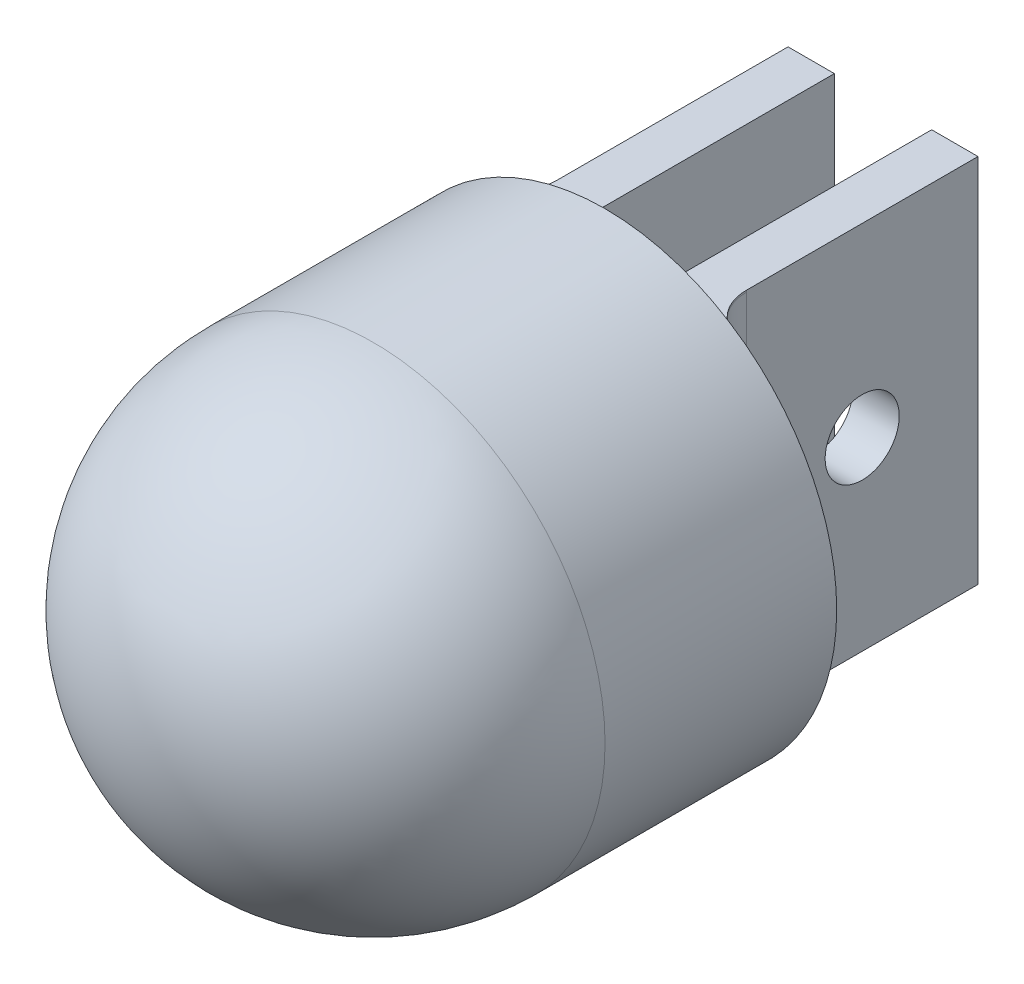
SolidWorks part; units mm, degrees
ref_plane "Front" through (0, 0, 0) normal (0, 0, 1) x (1, 0, 0)
ref_plane "Top" through (0, 0, 0) normal (0, 1, 0) x (1, 0, 0)
ref_plane "Right" through (0, 0, 0) normal (1, 0, 0) x (0, 0, -1)
sketch "草图2" plane through (0, 0, 0) normal (0, 1, 0) x (1, 0, 0)
  line L0 (0, 0) -> (0, 11.3858) construction
  line L1 (0, 10) -> (-5, 10)
  line L2 (-5, 10) -> (-5, 5)
  line L3 (0, 0) -> (0, 10)
  arc A0 (-5, 5) -> (0, 0) centre (0, 5) ccw
  point P8 (-2.5, 10)
  dimension "D2" = 10
  dimension "D1" = 10
revolve "旋转1" add sketch "草图2" angle 360 about L0
sketch "草图3" plane through (0, 0, -10) normal (0, 0, -1) x (-1, 0, 0)
  line L0 (0, 0) -> (0, 3.9434) construction
  line L1 (-2.05, 4) -> (-1.05, 4)
  line L2 (-2.05, 4) -> (-2.05, -4)
  line L3 (-2.05, -4) -> (-1.05, -4)
  line L4 (-1.05, 4) -> (-1.05, -4)
  line L5 (1.05, 4) -> (2.05, 4)
  line L6 (1.05, 4) -> (1.05, -4)
  line L7 (1.05, -4) -> (2.05, -4)
  line L8 (2.05, 4) -> (2.05, -4)
  line L9 (-1.05, 0) -> (1.05, 0) construction
  dimension "D1" = 2.1
  dimension "D2" = 1
  dimension "D3" = 1
  dimension "D4" = 8
extrude "凸台-拉伸1" add sketch "草图3" along normal blind 6
hole_wizard "M2 螺纹孔1" positions "草图4" profile "草图5" tap size "M2" standard "GB"
sketch "草图4" plane through (-2.05, 0, 0) normal (-1, 0, 0) x (0, 0, 1)
  line L0 (-16, -4) -> (-16, 4) construction
  point P0 (-13.5, 0)
  dimension "D1" = 2.5
sketch "草图5" plane through (-2.05, 0, -13.5) normal (0, 1, 0) x (0, 0, 1)
  line L0 (0, 0) -> (0, 5.6807)
  line L1 (0, 5.6807) -> (0.8, 5.2)
  line L2 (0.8, 5.2) -> (0.8, 0)
  line L5 (0.8, 0) -> (0, 0)
  line L10 (0, 5.6807) -> (-0.8, 5.2) construction
  line L11 (0, -6.35) -> (0, 107.95) construction
  dimension "螺纹孔钻头直径" = 1.6
  dimension "螺纹孔钻头深度" = 5.2
  dimension "导头角度" = 118
cosmetic thread "孔螺蚊线1" parameters "D1"=4, "D2"=2
fillet "圆角1" radius 1 2 edges at (2.05, 0, -10) (-2.05, 0, -10)
